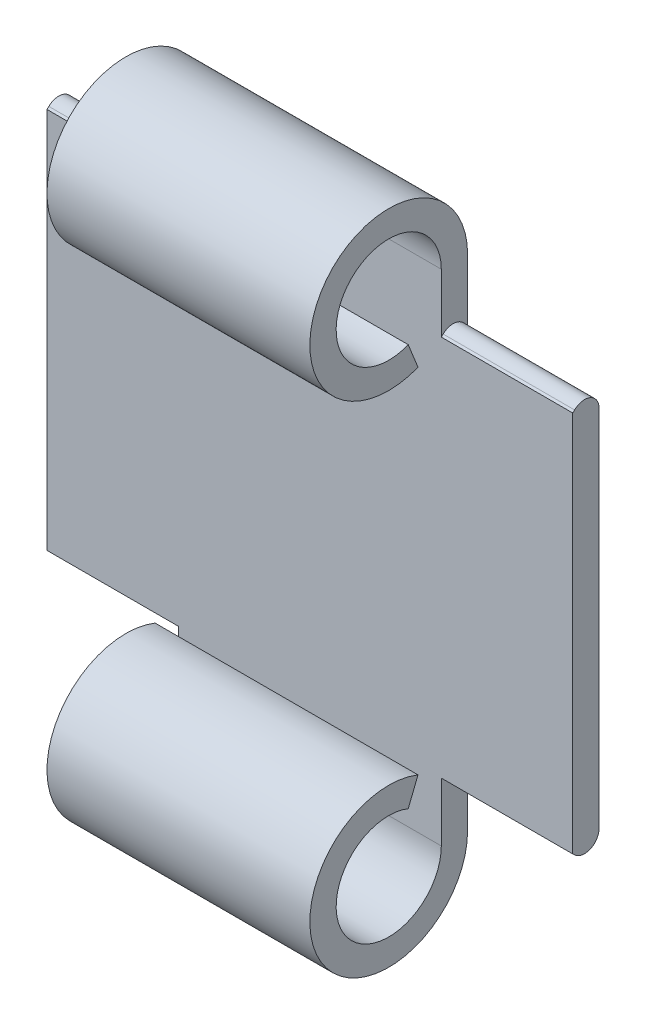
SolidWorks part; units mm, degrees
ref_plane "Front Plane" through (0, 0, 0) normal (0, 0, 1) x (1, 0, 0)
ref_plane "Top Plane" through (0, 0, 0) normal (0, 1, 0) x (1, 0, 0)
ref_plane "Right Plane" through (0, 0, 0) normal (1, 0, 0) x (0, 0, -1)
sketch "Sketch1" plane through (0, 0, 0) normal (0, 0, 1) x (1, 0, 0)
  line L1 (0, 0) -> (40, 0)
  line L2 (0, 0) -> (0, 50)
  line L3 (0, 50) -> (40, 50)
  line L4 (40, 0) -> (40, 50)
  dimension "D1" = 50
  dimension "D2" = 40
extrude "Boss-Extrude1" add sketch "Sketch1" along normal blind 2
sketch "Sketch3" plane through (0, 0, 2) normal (0, 0, 1) x (1, 0, 0)
  line L0 (40, 0) -> (40, 50) construction
  line L1 (0, 0) -> (40, 0)
  line L2 (0, 0) -> (0, 6)
  line L3 (0, 6) -> (40, 6)
  line L4 (40, 0) -> (40, 6)
  dimension "D1" = 6
extrude "Cut-Extrude3" cut sketch "Sketch3" against normal blind 3 contours L3 L4 L1 L2
sketch "Sketch8" plane through (0, 0, 2) normal (0, 0, 1) x (1, 0, 0)
  line L0 (40, 6) -> (40, 50) construction
  line L1 (0, 50) -> (40, 50)
  line L2 (0, 50) -> (0, 44)
  line L3 (0, 44) -> (40, 44)
  line L4 (40, 50) -> (40, 44)
  dimension "D1" = 6
extrude "Cut-Extrude4" cut sketch "Sketch8" against normal blind 10
ref_axis "Axis2" through (40, 25, 0) along (-1, 0, 0)
ref_axis "Axis3" through (40, 25, 2) along (-1, 0, 0)
ref_plane "Plane1" through (0, 25, 0) normal (0, -1, 0) x (-1, 0, 0)
ref_plane "Plane2" through (20, 0, 0) normal (1, 0, 0) x (0, 0, -1)
sketch "Sketch6" plane through (20, 0, -40) normal (-1, 0, 0) x (0, 0, 1)
  line L0 (43.7726, 11.5712) -> (44.5151, 9.7142)
  line L1 (42, 6) -> (40, 6)
  arc A0 (40, 6) -> (52, 6) centre (46, 6) ccw
  arc A1 (52, 6) -> (43.7726, 11.5712) centre (46, 6) ccw
  arc A2 (42, 6) -> (50, 6) centre (46, 6) ccw
  arc A3 (50, 6) -> (44.5151, 9.7142) centre (46, 6) ccw
  dimension "D1" = 6
extrude "Boss-Extrude2" add sketch "Sketch6" along normal blind 10 and the other way blind 10
mirror "Mirror2" about plane through (0, 25, 0) normal (0, -1, 0) of "Boss-Extrude2"
sketch "Sketch9" plane through (10, 0, 0) normal (-1, 0, 0) x (0, 0, 1)
  circle A0 centre (6, 6) radius 6
extrude "Cut-Extrude5" cut sketch "Sketch9" along normal blind 10
mirror "Mirror3" about plane through (20, 0, 0) normal (1, 0, 0) of "Cut-Extrude5"
mirror "Mirror4" about plane through (0, 25, 0) normal (0, -1, 0) of "Cut-Extrude5", "Mirror3"
fillet "Fillet1" radius 1.1 4 edges at (5, 6, 0) (5, 44, 0) (35, 6, 0) (35, 44, 0)
